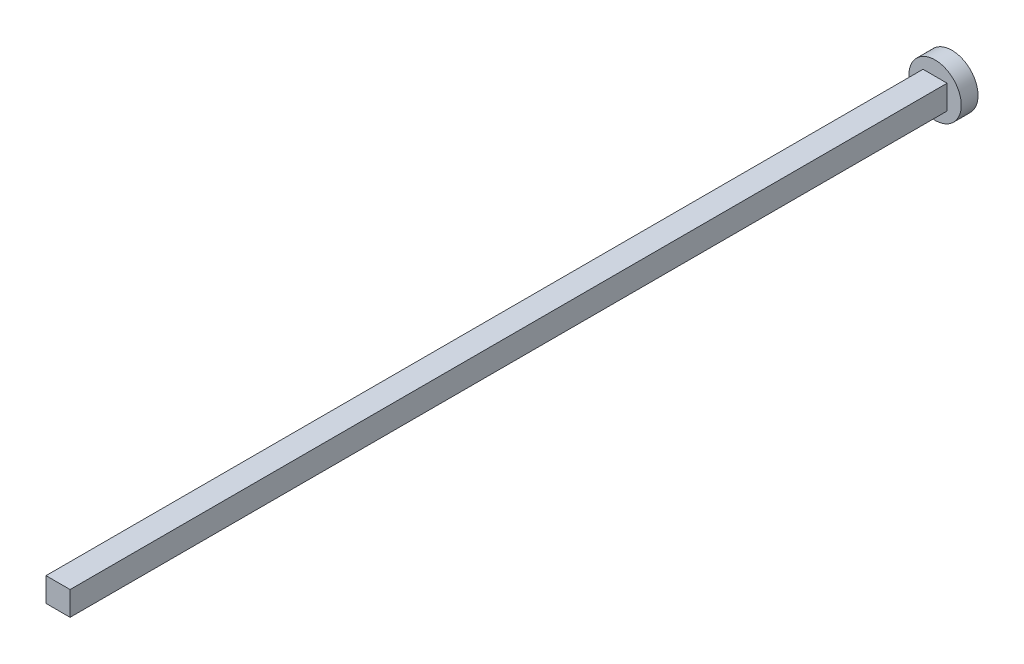
SolidWorks part; units mm, degrees
ref_plane "Front Plane" through (0, 0, 0) normal (0, 0, 1) x (1, 0, 0)
ref_plane "Top Plane" through (0, 0, 0) normal (0, 1, 0) x (1, 0, 0)
ref_plane "Right Plane" through (0, 0, 0) normal (1, 0, 0) x (0, 0, -1)
sketch "Sketch1" plane through (0, 0, 0) normal (0, 0, 1) x (1, 0, 0)
  line L1 (-1.4338, -1.4338) -> (1.4338, -1.4338)
  line L2 (-1.4338, -1.4338) -> (-1.4338, 1.4338)
  line L3 (-1.4338, 1.4338) -> (1.4338, 1.4338)
  line L4 (1.4338, -1.4338) -> (1.4338, 1.4338)
  line L5 (-1.4338, -1.4338) -> (1.4338, 1.4338) construction
  line L6 (-1.4338, 1.4338) -> (1.4338, -1.4338) construction
  point P0 (0, 0)
  dimension "D1" = 2.8676
extrude "Boss-Extrude1" add sketch "Sketch1" along normal blind 104.37
sketch "Sketch2" plane through (0, 0, 0) normal (0, 0, -1) x (-1, 0, 0)
  circle A0 centre (0, 0) radius 3.1162
extrude "Boss-Extrude2" add sketch "Sketch2" along normal blind 2
ref_axis "Axis1" through (0, 0, -2) along (0, 0, 1)
